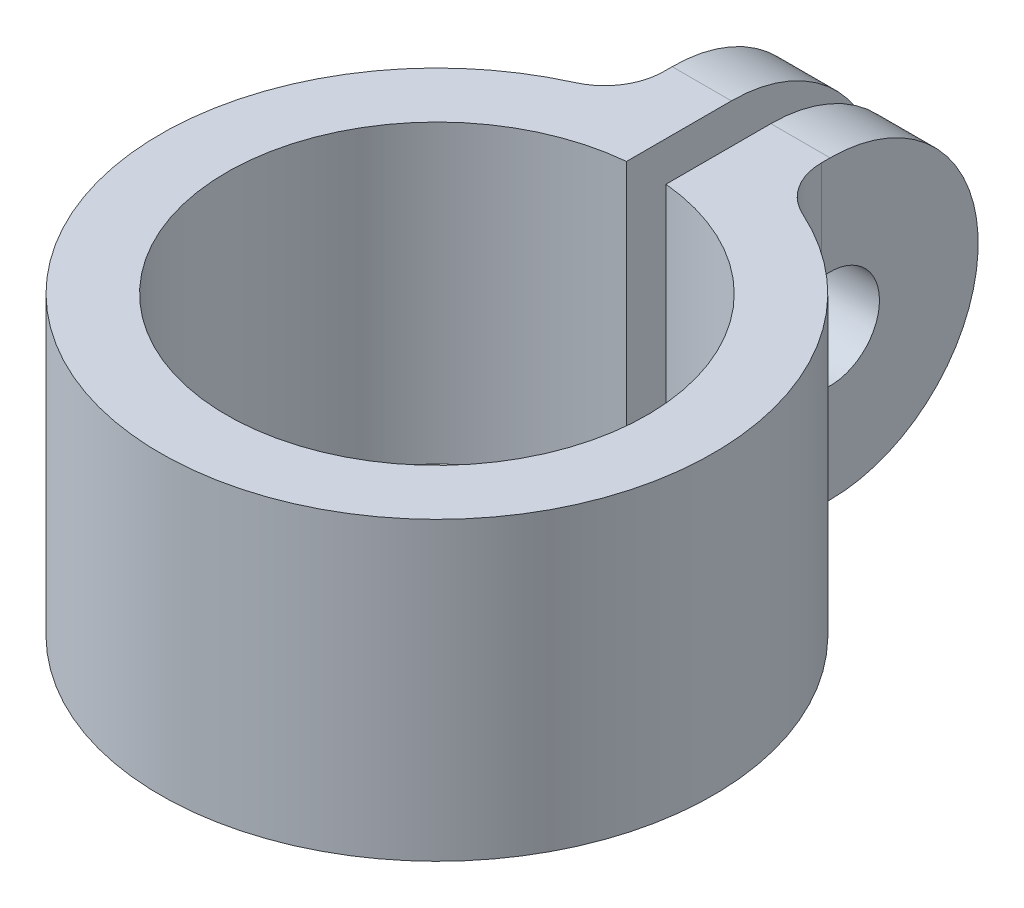
SolidWorks part; units mm, degrees
ref_plane "Front Plane" through (0, 0, 0) normal (0, 0, 1) x (1, 0, 0)
ref_plane "Top Plane" through (0, 0, 0) normal (0, 1, 0) x (1, 0, 0)
ref_plane "Right Plane" through (0, 0, 0) normal (1, 0, 0) x (0, 0, -1)
sketch "Sketch1" plane through (0, 0, 0) normal (0, 1, 0) x (1, 0, 0)
  line L0 (1, 10.6029) -> (1, 23.4164)
  line L1 (-1, 10.6029) -> (-1, 23.4164)
  line L2 (4, 23.4164) -> (4, 15.4919)
  line L3 (-4, 23.4164) -> (-4, 15.4919)
  line L4 (1, 23.4164) -> (4, 23.4164)
  line L5 (-1, 23.4164) -> (-4, 23.4164)
  arc A0 (-1, 10.6029) -> (1, 10.6029) centre (0, 0) ccw
  arc A1 (-5.7647, 12.7581) -> (5.7647, 12.7581) centre (0, 0) ccw
  arc A3 (4, 15.4919) -> (5.7647, 12.7581) centre (7, 15.4919) ccw
  arc A4 (-4, 15.4919) -> (-5.7647, 12.7581) centre (-7, 15.4919) cw
  point P13 (4, 13.4164)
  point P16 (-4, 13.4164)
  dimension "D1" = 21.3
  dimension "D2" = 28
  dimension "D9" = 3
  dimension "D3" = 3
  dimension "D4" = 3
  dimension "D5" = 1
  dimension "D6" = 1
  dimension "D7" = 10
  dimension "D8" = 10
extrude "Boss-Extrude1" add sketch "Sketch1" along normal blind 15
fillet "Fillet1" 2 edges at (-2.5, 15, -23.4164) (-2.5, 0, -23.4164) type full round first side face at (0, 15, -12.284) second side face at (0, 0, -12.284) middle face at (-2.5, 7.5, -23.4164)
fillet "Fillet2" 2 edges at (2.5, 15, -23.4164) (2.5, 0, -23.4164) type full round first side face at (0, 15, -10.784) second side face at (0, 0, -10.784) middle face at (2.5, 7.5, -23.4164)
sketch "Sketch2" plane through (4, 0, 0) normal (1, 0, 0) x (0, 0, -1)
  circle A0 centre (15.9164, 7.5) radius 2.5
  arc A1 (15.9164, 0) -> (15.9164, 15) centre (15.9164, 7.5) ccw construction
  dimension "D1" = 5
extrude "Cut-Extrude1" cut sketch "Sketch2" against normal up to surface (8 mm away) up to face at (-4, 7.5, -17.5792)
